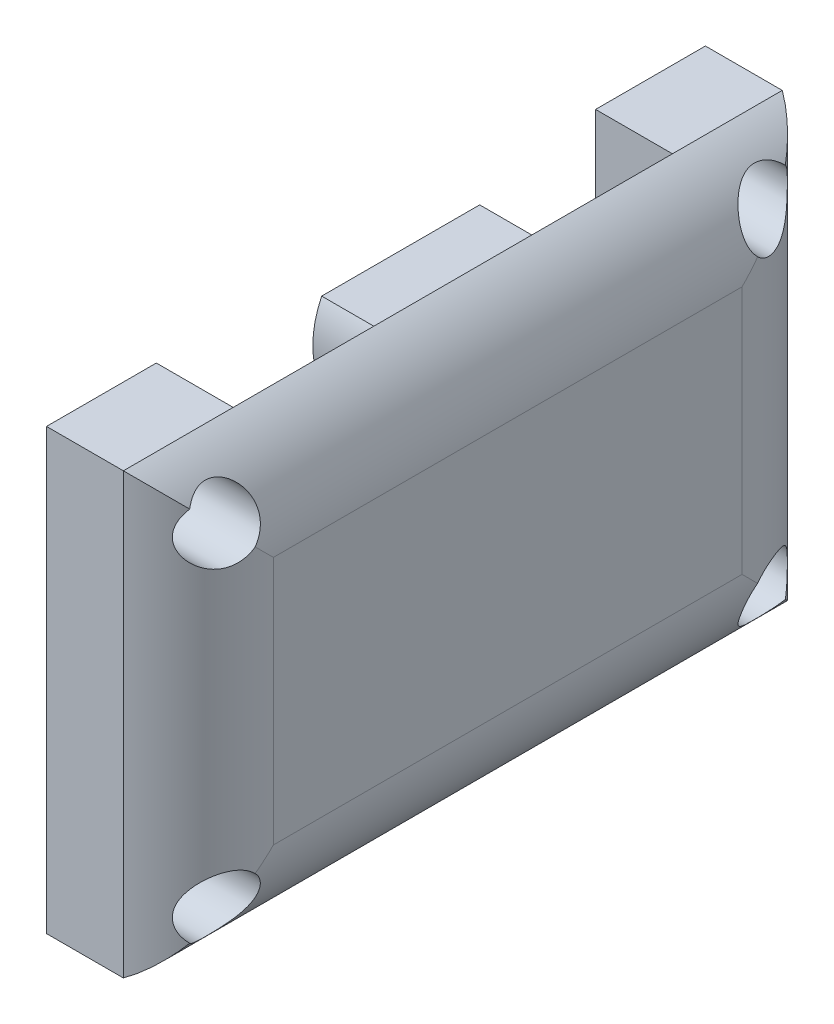
SolidWorks part; units mm, degrees
ref_plane "Alzado" through (0, 0, 0) normal (0, 0, 1) x (1, 0, 0)
ref_plane "Planta" through (0, 0, 0) normal (0, 1, 0) x (1, 0, 0)
ref_plane "Vista lateral" through (0, 0, 0) normal (1, 0, 0) x (0, 0, -1)
sketch "Croquis1" plane through (0, 0, 0) normal (1, 0, 0) x (0, 0, -1)
  line L1 (-30, -20) -> (30, -20)
  line L2 (-30, -20) -> (-30, 20)
  line L3 (-30, 20) -> (30, 20)
  line L4 (30, -20) -> (30, 20)
  line L5 (-30, -20) -> (30, 20) construction
  line L6 (-30, 20) -> (30, -20) construction
  point P0 (0, 0)
  dimension "D1" = 60
  dimension "D2" = 40
extrude "Saliente-Extruir1" add sketch "Croquis1" along normal blind 5
sketch "Croquis3" plane through (5, 0, 0) normal (1, 0, 0) x (0, 0, -1)
  line L0 (30, 20) -> (-30, 20) construction
  line L1 (-30, 20) -> (-30, -20) construction
  line L2 (0, 0) -> (0, 19.6817) construction
  line L3 (0, 0) -> (13.269, 0) construction
  circle A0 centre (-25, 15) radius 1.5
  circle A1 centre (25, 15) radius 1.5
  circle A2 centre (25, -15) radius 1.5
  circle A3 centre (-25, -15) radius 1.5
  dimension "D1" = 3
  dimension "D2" = 5
  dimension "D3" = 5
extrude "Cortar-Extruir1" cut sketch "Croquis3" against normal through all
fillet "Redondeo1" radius 10 4 edges at (5, -20, 0) (5, 20, 0) (5, 0, 30) (5, 0, -30)
sketch "Croquis5" plane through (5, 0, 0) normal (1, 0, 0) x (0, 0, -1)
  circle A0 centre (-25, 15) radius 3
  circle A1 centre (25, 15) radius 3
  circle A2 centre (25, -15) radius 3
  circle A3 centre (-25, -15) radius 3
  dimension "D1" = 6
  dimension "D2" = 6
  dimension "D3" = 6
  dimension "D4" = 6
extrude "Cortar-Extruir2" cut sketch "Croquis5" against normal blind 3.5
sketch "Croquis9" plane through (0, 0, 0) normal (-1, 0, 0) x (0, 0, 1)
  line L0 (30, -20) -> (-30, -20) construction
  line L1 (-30, 20) -> (-20, 20)
  line L2 (-30, 20) -> (-30, -20)
  line L3 (-30, -20) -> (-20, -20)
  line L4 (-20, 20) -> (-20, -20)
  line L6 (30, 20) -> (20, 20)
  line L7 (30, 20) -> (30, -20)
  line L8 (30, -20) -> (20, -20)
  line L9 (20, 20) -> (20, -20)
  dimension "D1" = 10
  dimension "D2" = 10
extrude "Saliente-Extruir3" add sketch "Croquis9" along normal blind 7
sketch "Croquis10" plane through (0, 0, 0) normal (1, 0, 0) x (0, 0, -1)
  circle A0 centre (-25, -15) radius 1.5 construction
  circle A1 centre (25, -15) radius 1.5 construction
  circle A2 centre (25, 15) radius 1.5 construction
  circle A3 centre (-25, 15) radius 1.5 construction
  circle A4 centre (-25, -15) radius 1.5
  circle A5 centre (25, -15) radius 1.5
  circle A6 centre (25, 15) radius 1.5
  circle A7 centre (-25, 15) radius 1.5
extrude "Cortar-Extruir5" cut sketch "Croquis10" against normal through all both and the other way through all
sketch "Croquis11" plane through (1.5, 0, 0) normal (1, 0, 0) x (0, 0, -1)
  circle A0 centre (-25, -15) radius 3 construction
  circle A1 centre (-25, 15) radius 3
  circle A2 centre (-25, 15) radius 3
  circle A3 centre (25, -15) radius 3
  circle A4 centre (25, -15) radius 3
  circle A5 centre (25, 15) radius 3 construction
  circle A6 centre (-25, -15) radius 3
  circle A7 centre (25, 15) radius 3
  dimension "D1" = 0
  dimension "D2" = 0
extrude "Cortar-Extruir6" cut sketch "Croquis11" against normal blind 6.63
sketch "Croquis12" plane through (0, 0, 0) normal (-1, 0, 0) x (0, 0, 1)
  line L0 (-5, 6.245) -> (-5, 10.255)
  line L3 (5, 6.245) -> (5, 10.255)
  line L4 (-7.1937, 20) -> (7.1937, 20)
  arc A0 (-5, 6.245) -> (5, 6.245) centre (0, 0) ccw
  arc A1 (5, 10.255) -> (7.1937, 20) centre (0, 16.5) ccw
  arc A2 (-7.1937, 20) -> (-5, 10.255) centre (0, 16.5) ccw
  dimension "D1" = 16
  dimension "D4" = 16
  dimension "D3" = 16.5
extrude "Saliente-Extruir4" add sketch "Croquis12" along normal up to surface (7 mm away) up to face at (-7, 15, -26.5)
sketch "Croquis13" plane through (-7, 0, 0) normal (-1, 0, 0) x (0, 0, 1)
  circle A0 centre (0, 0) radius 8
extrude "Cortar-Extruir7" cut sketch "Croquis13" against normal up to surface (7 mm away) up to face at (0, 5.7986, 0)
sketch "Croquis15" plane through (-7, 0, 0) normal (-1, 0, 0) x (0, 0, 1)
  line L3 (5, 6.245) -> (5, 10.255)
  line L4 (7.1937, 20) -> (-7.1937, 20)
  line L5 (-5, 10.255) -> (-5, 6.245)
  line L6 (5, 6.245) -> (5, 10.255)
  line L7 (7.1937, 20) -> (-7.1937, 20)
  line L8 (-5, 10.255) -> (-5, 6.245)
  arc A3 (5, 6.245) -> (-5, 6.245) centre (0, 0) ccw
  arc A4 (5, 10.255) -> (7.1937, 20) centre (0, 16.5) ccw
  arc A5 (-7.1937, 20) -> (-5, 10.255) centre (0, 16.5) ccw
  arc A6 (5, 6.245) -> (-5, 6.245) centre (0, 0) ccw
  arc A7 (5, 10.255) -> (7.1937, 20) centre (0, 16.5) ccw
  arc A8 (-7.1937, 20) -> (-5, 10.255) centre (0, 16.5) ccw
  dimension "D1" = 0
extrude "Cortar-Extruir8" cut sketch "Croquis15" against normal blind 2.25
